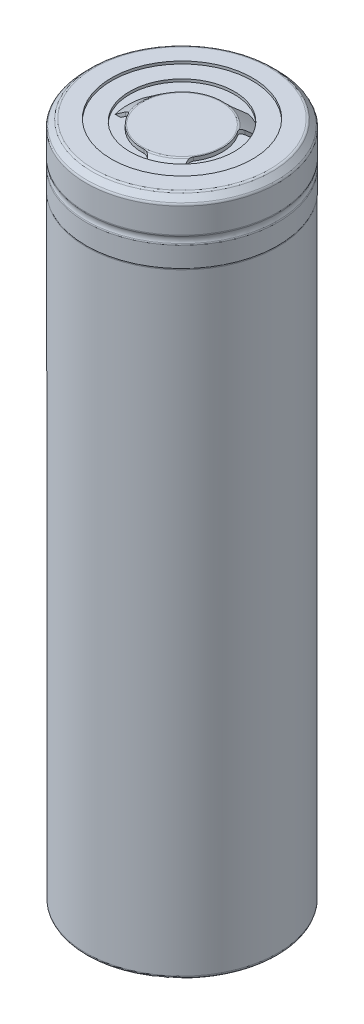
SolidWorks part; units mm, degrees
ref_plane "Ebene vorne" through (0, 0, 0) normal (0, 0, 1) x (1, 0, 0)
ref_plane "Ebene oben" through (0, 0, 0) normal (0, 1, 0) x (1, 0, 0)
ref_plane "Ebene rechts" through (0, 0, 0) normal (1, 0, 0) x (0, 0, -1)
sketch "Sketch1" plane through (0, 0, 0) normal (0, 0, 1) x (1, 0, 0)
  line L0 (0, 66.5966) -> (0, -169.2654) construction
  line L1 (0, -55) -> (0, 55) construction
  line L2 (0, 37.6239) -> (-3.7525, 37.6239)
  line L3 (-3.9289, 37.5666) -> (-5.2264, 36.6239)
  line L4 (-5.2264, 36.6239) -> (-8.54, 36.6239)
  line L5 (-8.54, 36.6239) -> (-8.54, 37.6239)
  line L6 (-8.54, 37.6239) -> (-5, 37.6239)
  line L7 (-5, 37.6239) -> (-5, 37.8739)
  line L8 (-5, 37.8739) -> (-6.75, 37.8739)
  line L9 (-6.75, 37.8739) -> (-6.75, 38.1239)
  line L10 (-6.75, 38.1239) -> (-8.54, 38.1239)
  line L11 (-8.54, 38.1239) -> (-9.19, 37.4739)
  line L12 (-9.19, 37.4739) -> (-9.19, 34.8739)
  line L13 (-9.19, 34.1739) -> (-9.19, 32.1739)
  line L14 (-9.19, 32.1739) -> (-9.16, 32.1739)
  line L15 (-9.16, 32.1739) -> (-9.16, -26.8261)
  line L16 (-9.16, -26.8261) -> (-6.75, -26.8261)
  line L17 (-6.75, -26.8261) -> (-6.75, -26.5761)
  line L18 (-6.75, -26.5761) -> (0, -26.5761)
  line L19 (0, -26.5761) -> (0, 37.6239)
  line L20 (-9.1, 35.1081) -> (-9.1, 20.1498) construction
  line L21 (-4.716, 36.6239) -> (-3.7525, 37.3239)
  line L22 (-3.7525, 37.3239) -> (-1.5, 37.3239)
  line L23 (-1.5, 37.3239) -> (-1.5, 36.6239)
  line L24 (-1.5, 36.6239) -> (-4.716, 36.6239)
  arc A0 (-9.19, 34.8739) -> (-9.19, 34.1739) centre (-9.8256, 34.5239) cw
  arc A1 (-3.9289, 37.5666) -> (-3.7525, 37.6239) centre (-3.7525, 37.3239) cw
  point P41 (-3.85, 37.6239)
  dimension "D1" = 18.38
  dimension "D5" = 9.1
  dimension "D19" = 0.3
  dimension "D2" = 0.25
  dimension "D3" = 13.5
  dimension "D4" = 18.32
  dimension "D6" = 0.7
  dimension "D7" = 45
  dimension "D8" = 0.65
  dimension "D9" = 13.5
  dimension "D10" = 0.25
  dimension "D11" = 10
  dimension "D12" = 0.25
  dimension "D13" = 1.5
  dimension "D14" = 7.7
  dimension "D15" = 36
  dimension "D16" = 59
  dimension "D17" = 61
  dimension "D18" = 64.95
  dimension "D20" = 3
revolve "Revolve1" add sketch "Sketch1" angle 360 about L0
sketch "Sketch3" plane through (0, 37.6239, 0) normal (0, 1, 0) x (1, 0, 0)
  line L0 (-9.8854, 0) -> (0, 0) construction
  line L1 (-55, 0) -> (55, 0) construction
  line L2 (-5.049, -1.35) -> (-3.6056, -1.35)
  line L3 (0, 0) -> (-5.5721, -9.6512) construction
  line L4 (1.3554, -5.0476) -> (0.6336, -3.7975)
  line L5 (1.3554, 5.0476) -> (0.6336, 3.7975)
  line L6 (-5.049, 1.35) -> (-3.6056, 1.35)
  line L7 (3.6936, 3.6976) -> (2.9719, 2.4475)
  line L8 (3.6936, -3.6976) -> (2.9719, -2.4475)
  circle A0 centre (0, 0) radius 5.2264 construction
  circle A1 centre (0, 0) radius 5.2264 construction
  circle A2 centre (0, 0) radius 3.85 construction
  arc A3 (-3.6056, -1.35) -> (0.6336, -3.7975) centre (0, 0) ccw
  arc A4 (-5.049, -1.35) -> (1.3554, -5.0476) centre (0, 0) ccw
  arc A5 (-5.049, 1.35) -> (1.3554, 5.0476) centre (0, 0) cw
  arc A6 (-3.6056, 1.35) -> (0.6336, 3.7975) centre (0, 0) cw
  arc A7 (2.9719, -2.4475) -> (2.9719, 2.4475) centre (0, 0) ccw
  arc A8 (3.6936, -3.6976) -> (3.6936, 3.6976) centre (0, 0) ccw
  dimension "D1" = 1.35
  dimension "D2" = 60
extrude "Cut-Extrude1" cut sketch "Sketch3" against normal up to surface (1 mm away) up to face at (0, 36.6239, 8.54)
fillet "Fillet1" radius 0.3 6 edges at (0, -26.8261, 9.16) (0, 38.1239, 8.54) (0, 37.4739, 9.19) (0, 32.1739, 9.16) (0, 34.1739, 9.19) (0, 34.8739, 9.19)
fillet "Fillet3" radius 0.7 6 edges at (-3.6056, 37.4304, -1.35) (0.6336, 37.4304, -3.7975) (2.9719, 37.4304, -2.4475) (2.9719, 37.4304, 2.4475) (0.6336, 37.4304, 3.7975) (-3.6056, 37.4304, 1.35)
